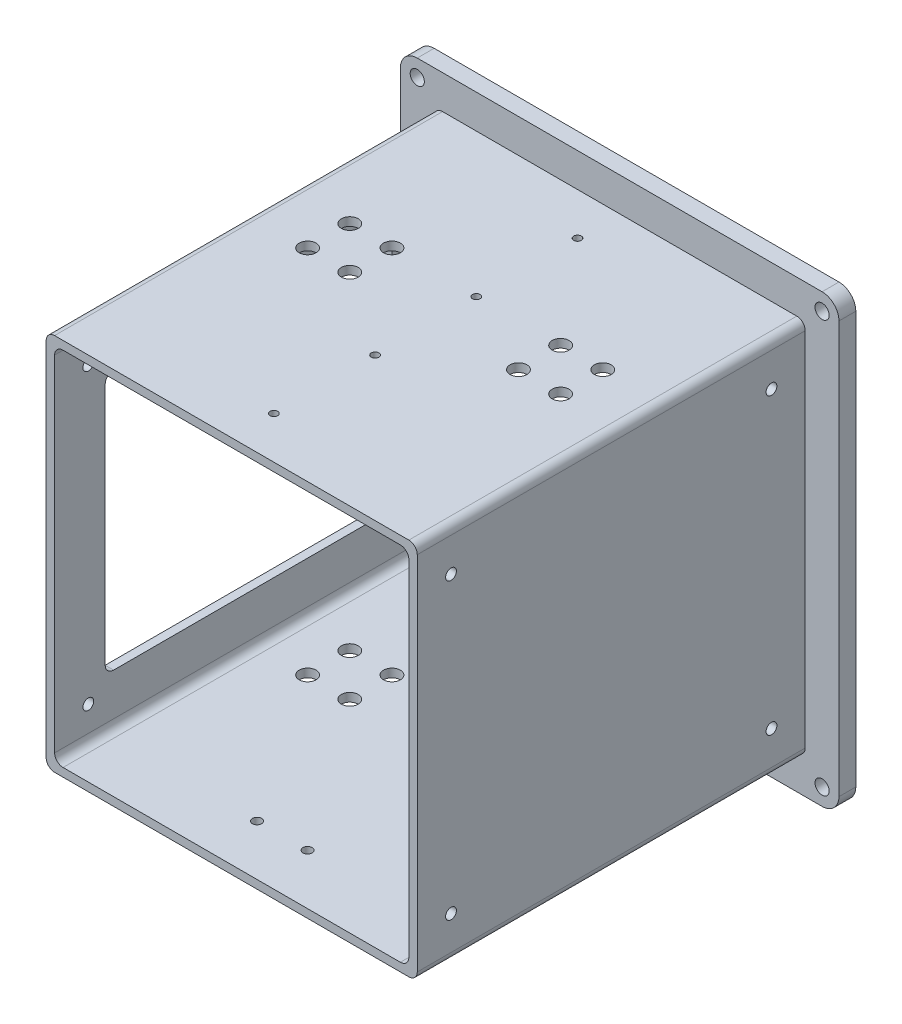
SolidWorks part; units mm, degrees
ref_plane "前视基准面" through (0, 0, 0) normal (0, 0, 1) x (1, 0, 0)
ref_plane "上视基准面" through (0, 0, 0) normal (0, 1, 0) x (1, 0, 0)
ref_plane "右视基准面" through (0, 0, 0) normal (1, 0, 0) x (0, 0, -1)
sketch "草图1" plane through (0, 0, 0) normal (0, 0, 1) x (1, 0, 0)
  line L1 (-105, -107.125) -> (105, -107.125)
  line L2 (-105, -107.125) -> (-105, 107.125)
  line L3 (-105, 107.125) -> (105, 107.125)
  line L4 (105, -107.125) -> (105, 107.125)
  line L5 (-105, -107.125) -> (105, 107.125) construction
  line L6 (-105, 107.125) -> (105, -107.125) construction
  line L7 (-110, -112.125) -> (110, -112.125)
  line L8 (-110, -112.125) -> (-110, 112.125)
  line L9 (-110, 112.125) -> (110, 112.125)
  line L10 (110, -112.125) -> (110, 112.125)
  line L11 (-110, -112.125) -> (110, 112.125) construction
  line L12 (-110, 112.125) -> (110, -112.125) construction
  point P0 (0, 0)
  point P6 (0, 0)
  dimension "D1" = 210
  dimension "D2" = 214.25
  dimension "D3" = 5
  dimension "D4" = 5
extrude "凸台-拉伸1" add sketch "草图1" along normal blind 230
sketch "草图2" plane through (0, 0, 0) normal (0, 0, -1) x (-1, 0, 0)
  line L0 (-110, 112.125) -> (110, 112.125) construction
  line L1 (-130, -132.125) -> (130, -132.125)
  line L2 (-130, -132.125) -> (-130, 132.125)
  line L3 (-130, 132.125) -> (130, 132.125)
  line L4 (130, -132.125) -> (130, 132.125)
  line L5 (-130, -132.125) -> (130, 132.125) construction
  line L6 (-130, 132.125) -> (130, -132.125) construction
  line L7 (-110, -112.125) -> (-110, 112.125) construction
  line L8 (105, 107.125) -> (105, -107.125) construction
  line L9 (105, -107.125) -> (-105, -107.125) construction
  line L10 (-105, -107.125) -> (-105, 107.125) construction
  line L11 (-105, 107.125) -> (105, 107.125) construction
  line L12 (105, 107.125) -> (105, -107.125)
  line L13 (105, -107.125) -> (-105, -107.125)
  line L14 (-105, -107.125) -> (-105, 107.125)
  line L15 (-105, 107.125) -> (105, 107.125)
  point P0 (0, 0)
  dimension "D1" = 20
  dimension "D2" = 20
extrude "凸台-拉伸2" add sketch "草图2" along normal blind 10
fillet "圆角1" radius 5 4 edges at (110, 112.125, 115) (110, -112.125, 115) (-110, -112.125, 115) (-110, 112.125, 115)
fillet "圆角2" radius 5 4 edges at (105, 107.125, 110) (-105, 107.125, 110) (105, -107.125, 110) (-105, -107.125, 110)
fillet "圆角3" radius 10 4 edges at (-130, 132.125, -5) (130, 132.125, -5) (130, -132.125, -5) (-130, -132.125, -5)
hole_wizard "Ø8.4 (8.4) 直径孔1" positions "草图3" profile "草图4" hole size "Ø8.4" standard "GB" end condition through all
sketch "草图3" plane through (0, 0, 0) normal (0, 0, 1) x (1, 0, 0)
  point P0 (120, 122.125)
  point P3 (120, -122.125)
  point P6 (-120, -122.125)
  point P10 (-120, 122.125)
sketch "草图4" plane through (120, 122.125, 0) normal (1, 0, 0) x (0, -1, 0)
  line L0 (0, 0) -> (0, 10)
  line L1 (0, 10) -> (4.2, 10)
  line L2 (4.2, 10) -> (4.2, 0)
  line L5 (4.2, 0) -> (0, 0)
  line L11 (0, -6.35) -> (0, 107.95) construction
  dimension "通孔孔直径" = 8.4
  dimension "通孔孔深度" = 10
sketch "草图18" plane through (0, 112.125, 0) normal (0, 1, 0) x (1, 0, 0)
  line L0 (105, -230) -> (-105, -230) construction
  line L1 (-105, 0) -> (-105, -230) construction
  line L2 (105, -230) -> (105, 0) construction
  point P0 (-75, -85)
  point P1 (-75, -110)
  point P2 (-50, -110)
  point P3 (-50, -85)
  point P5 (50, -110)
  point P6 (75, -110)
  point P8 (75, -85)
  point P16 (50, -85)
  dimension "D1" = 25
  dimension "D2" = 25
  dimension "D3" = 35.3553
  dimension "D4" = 25
  dimension "D5" = 35.3553
  dimension "D6" = 25
  dimension "D7" = 30
  dimension "D8" = 30
  dimension "D9" = 25
  dimension "D10" = 25
  dimension "D11" = 25
  dimension "D12" = 25
  dimension "D13" = 120
  dimension "D14" = 120
  dimension "D15" = 35.3553
  dimension "D16" = 55
hole_wizard "大小mm 暗销孔11" positions "草图33" profile "草图34" hole size "Ø10.0" standard "GB" end condition through all
sketch "草图33" plane through (0, 112.125, 0) normal (0, 1, 0) x (1, 0, 0)
  point P0 (-75, -85)
  point P3 (-50, -85)
  point P6 (-50, -110)
  point P9 (-75, -110)
  point P12 (50, -110)
  point P15 (50, -85)
  point P18 (75, -85)
  point P21 (75, -110)
sketch "草图34" plane through (-75, 112.125, 85) normal (1, 0, 0) x (0, 0, 1)
  line L0 (0, 0) -> (0, 244.25)
  line L1 (0, 244.25) -> (5, 244.25)
  line L2 (5, 244.25) -> (5, 0)
  line L5 (5, 0) -> (0, 0)
  line L11 (0, -6.35) -> (0, 107.95) construction
  dimension "通孔孔直径" = 10
  dimension "通孔孔深度" = 244.25
sketch "草图35" plane through (0, -112.125, 0) normal (0, -1, 0) x (1, 0, 0)
  line L0 (120, 0) -> (-120, 0) construction
  line L2 (-105, 0) -> (105, 0) construction
  line L3 (105, 0) -> (105, 230) construction
  line L4 (-105, 230) -> (-105, 0) construction
  point P0 (15, 200)
  point P1 (19, 25.5)
  point P2 (-19, 25.5)
  point P4 (-15, 200)
  dimension "D1" = 90
  dimension "D2" = 38
  dimension "D4" = 19
  dimension "D5" = 200
  dimension "D6" = 200
  dimension "D7" = 25.5
  dimension "D8" = 25.5
  dimension "D9" = 90
sketch "草图38" plane through (0, 112.125, 0) normal (0, 1, 0) x (1, 0, 0)
  line L0 (-105, 0) -> (-105, -230) construction
  line L2 (105, 0) -> (-105, 0) construction
  point P0 (0, -25)
  point P1 (0, -85)
  point P2 (0, -205)
  point P3 (0, -145)
  dimension "D1" = 105
  dimension "D2" = 60
  dimension "D3" = 60
  dimension "D4" = 60
  dimension "D5" = 25
  dimension "D6" = 105
  dimension "D7" = 105
  dimension "D8" = 105
hole_wizard "Ø4.5 (4.5) 直径孔1" positions "草图39" profile "草图40" hole size "Ø4.5" standard "GB" end condition up to next
sketch "草图39" plane through (0, 112.125, 0) normal (0, 1, 0) x (1, 0, 0)
  point P0 (0, -25)
  point P3 (0, -85)
  point P6 (0, -145)
  point P9 (0, -205)
sketch "草图40" plane through (0, 112.125, 25) normal (1, 0, 0) x (0, 0, 1)
  line L0 (0, 0) -> (0, 5)
  line L1 (0, 5) -> (2.25, 5)
  line L2 (2.25, 5) -> (2.25, 0)
  line L5 (2.25, 0) -> (0, 0)
  line L11 (0, -6.35) -> (0, 107.95) construction
  dimension "通孔孔直径" = 4.5
  dimension "通孔孔深度" = 5
hole_wizard "Ø6.6 (6.6) 直径孔1" positions "草图41" profile "草图42" hole size "Ø6.6" standard "GB" end condition up to next
sketch "草图41" plane through (0, -112.125, 0) normal (0, -1, 0) x (-1, 0, 0)
  point P0 (19, -25.5)
  point P3 (-19, -25.5)
sketch "草图42" plane through (-19, -112.125, 25.5) normal (1, 0, 0) x (0, 0, -1)
  line L0 (0, 0) -> (0, 5)
  line L1 (0, 5) -> (3.3, 5)
  line L2 (3.3, 5) -> (3.3, 0)
  line L5 (3.3, 0) -> (0, 0)
  line L11 (0, -6.35) -> (0, 107.95) construction
  dimension "通孔孔直径" = 6.6
  dimension "通孔孔深度" = 5
hole_wizard "Ø5.5 (5.5) 直径孔1" positions "草图43" profile "草图44" hole size "Ø5.5" standard "GB" end condition up to next
sketch "草图43" plane through (0, -112.125, 0) normal (0, -1, 0) x (-1, 0, 0)
  point P0 (15, -200)
  point P3 (-15, -200)
sketch "草图44" plane through (-15, -112.125, 200) normal (1, 0, 0) x (0, 0, -1)
  line L0 (0, 0) -> (0, 5)
  line L1 (0, 5) -> (2.75, 5)
  line L2 (2.75, 5) -> (2.75, 0)
  line L5 (2.75, 0) -> (0, 0)
  line L11 (0, -6.35) -> (0, 107.95) construction
  dimension "通孔孔直径" = 5.5
  dimension "通孔孔深度" = 5
sketch "草图45" plane through (-110, 0, 0) normal (-1, 0, 0) x (0, 0, 1)
  line L0 (230, 107.125) -> (0, 107.125) construction
  line L1 (200, -77.125) -> (30, -77.125)
  line L2 (200, -77.125) -> (200, 77.125)
  line L3 (200, 77.125) -> (30, 77.125)
  line L4 (30, -77.125) -> (30, 77.125)
  line L5 (200, -77.125) -> (30, 77.125) construction
  line L6 (200, 77.125) -> (30, -77.125) construction
  line L7 (0, -107.125) -> (230, -107.125) construction
  line L8 (0, -122.125) -> (0, 122.125) construction
  line L9 (230, 107.125) -> (230, -107.125) construction
  point P0 (115, 0)
  dimension "D1" = 30
  dimension "D2" = 30
  dimension "D3" = 30
  dimension "D4" = 30
extrude "切除-拉伸1" cut sketch "草图45" against normal up to next
fillet "圆角4" radius 5 4 edges at (-107.5, -77.125, 30) (-107.5, -77.125, 200) (-107.5, 77.125, 200) (-107.5, 77.125, 30)
sketch "草图46" plane through (110, 0, 0) normal (1, 0, 0) x (0, 0, -1)
  line L0 (-195, 77.125) -> (-35, 77.125) construction
  line L1 (-200, -72.125) -> (-200, 72.125) construction
  line L2 (-30, 72.125) -> (-30, -72.125) construction
  line L3 (-35, -77.125) -> (-195, -77.125) construction
  point P0 (-210, 87.125)
  point P1 (-210, -87.125)
  point P2 (-20, -87.125)
  point P3 (-20, 87.125)
  dimension "D1" = 10
  dimension "D2" = 10
  dimension "D3" = 10
  dimension "D4" = 10
  dimension "D5" = 10
  dimension "D6" = 10
  dimension "D7" = 10
  dimension "D8" = 10
hole_wizard "Ø6.4 (6.4) 直径孔1" positions "草图47" profile "草图48" hole size "Ø6.4" standard "GB" end condition through all
sketch "草图47" plane through (110, 0, 0) normal (1, 0, 0) x (0, 0, -1)
  point P0 (-210, 87.125)
  point P3 (-20, 87.125)
  point P6 (-20, -87.125)
  point P9 (-210, -87.125)
sketch "草图48" plane through (110, 87.125, 210) normal (0, 1, 0) x (0, 0, -1)
  line L0 (0, 0) -> (0, 240)
  line L1 (0, 240) -> (3.2, 240)
  line L2 (3.2, 240) -> (3.2, 0)
  line L5 (3.2, 0) -> (0, 0)
  line L11 (0, -6.35) -> (0, 107.95) construction
  dimension "通孔孔直径" = 6.4
  dimension "通孔孔深度" = 240
